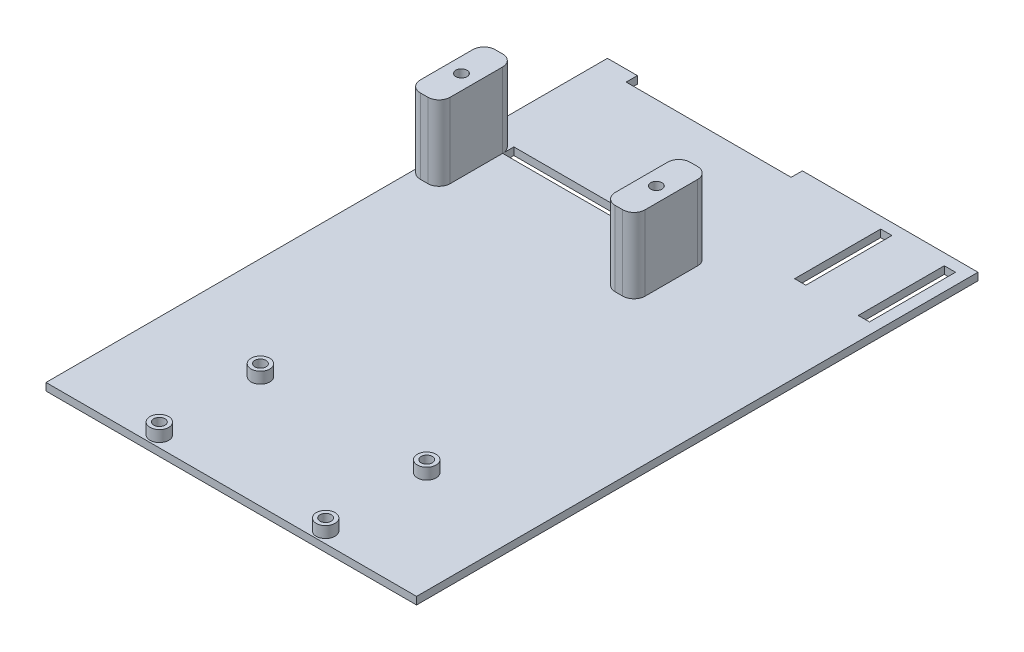
SolidWorks part; units mm, degrees
ref_plane "Front Plane" through (0, 0, 0) normal (0, 0, 1) x (1, 0, 0)
ref_plane "Top Plane" through (0, 0, 0) normal (0, 1, 0) x (1, 0, 0)
ref_plane "Right Plane" through (0, 0, 0) normal (1, 0, 0) x (0, 0, -1)
sketch "Sketch1" plane through (0, 0, 0) normal (0, 1, 0) x (1, 0, 0)
  line L1 (0, 0) -> (99, 0)
  line L2 (0, 0) -> (0, 150)
  line L3 (0, 150) -> (99, 150)
  line L4 (99, 0) -> (99, 150)
  dimension "D1" = 99
  dimension "D2" = 150
extrude "Boss-Extrude1" add sketch "Sketch1" along normal blind 2
sketch "Sketch2" plane through (0, 2, 0) normal (0, 1, 0) x (1, 0, 0)
  line L0 (0, 117) -> (8, 117)
  line L2 (8, 117) -> (8, 97)
  line L3 (8, 97) -> (0, 97)
  line L4 (0, 150) -> (0, 0) construction
  line L5 (0, 97) -> (0, 117)
  line L6 (0, 117) -> (60.075, 117) construction
  line L7 (99, 150) -> (0, 150) construction
  line L8 (60.075, 117) -> (52.075, 117)
  line L9 (60.075, 117) -> (60.075, 97)
  line L10 (60.075, 97) -> (52.075, 97)
  line L11 (52.075, 117) -> (52.075, 97)
  dimension "D1" = 8
  dimension "D2" = 20
  dimension "D3" = 60.075
  dimension "D4" = 8
  dimension "D5" = 20
  dimension "D6" = 33
extrude "Boss-Extrude2" add sketch "Sketch2" along normal blind 20 contours L5 L0 L2 L3 | L9 L8 L11 L10
sketch "Sketch3" plane through (0, 22, 0) normal (0, 1, 0) x (1, 0, 0)
  line L4 (0, 107) -> (8, 107) construction
  line L5 (0, 97) -> (0, 117) construction
  line L6 (8, 117) -> (8, 97) construction
  line L9 (52.075, 107) -> (60.075, 107) construction
  line L10 (52.075, 117) -> (52.075, 97) construction
  line L11 (60.075, 117) -> (60.075, 97) construction
  circle A0 centre (4, 107) radius 1.5
  circle A2 centre (56.075, 107) radius 1.5
  point P2 (4, 109)
  dimension "D1" = 3
  dimension "D2" = 3
  dimension "D3" = 4
  dimension "D4" = 4
  dimension "D5" = 0
extrude "Cut-Extrude2" cut sketch "Sketch3" against normal blind 15 contours A2 | A0 region at (56.075, 22, -107)
sketch "Sketch4" plane through (0, 2, 0) normal (0, 1, 0) x (1, 0, 0)
  line L0 (49.5, 0) -> (49.5, 69.0338) construction
  line L1 (0, 0) -> (99, 0) construction
  line L2 (27.29, 3) -> (71.71, 3) construction
  line L3 (27.29, 3) -> (27.29, 30) construction
  line L4 (27.29, 30) -> (71.71, 30) construction
  line L5 (71.71, 30) -> (71.71, 3) construction
  circle A0 centre (27.29, 30) radius 1.5
  circle A1 centre (71.71, 30) radius 1.5
  circle A2 centre (71.71, 3) radius 1.5
  circle A3 centre (27.29, 3) radius 1.5
  circle A4 centre (27.29, 30) radius 2.5
  circle A5 centre (71.71, 30) radius 2.5
  circle A6 centre (71.71, 3) radius 2.5
  circle A7 centre (27.29, 3) radius 2.5
  dimension "D5" = 3
  dimension "D6" = 3
  dimension "D7" = 3
  dimension "D8" = 3
  dimension "D9" = 5
  dimension "D10" = 5
  dimension "D11" = 5
  dimension "D12" = 5
  dimension "D1" = 3
  dimension "D2" = 44.42
  dimension "D3" = 22.21
  dimension "D4" = 27
extrude "Boss-Extrude4" add sketch "Sketch4" along normal blind 3
sketch "Sketch6" plane through (0, 2, 0) normal (0, 1, 0) x (1, 0, 0)
  line L0 (52.075, 117) -> (52.075, 97) construction
  line L1 (8, 117) -> (52.075, 117)
  line L2 (8, 117) -> (8, 114)
  line L3 (8, 114) -> (52.075, 114)
  line L4 (52.075, 117) -> (52.075, 114)
  line L5 (99, 150) -> (0, 150) construction
  line L6 (8, 150) -> (52.075, 150)
  line L7 (8, 150) -> (8, 147)
  line L8 (8, 147) -> (52.075, 147)
  line L9 (52.075, 150) -> (52.075, 147)
  line L10 (99, 0) -> (99, 150) construction
  line L11 (96, 147) -> (93, 147)
  line L12 (96, 147) -> (96, 124)
  line L13 (96, 124) -> (93, 124)
  line L14 (93, 147) -> (93, 124)
  line L15 (93, 147) -> (79, 147) construction
  line L17 (79, 147) -> (76, 147)
  line L18 (79, 147) -> (79, 124)
  line L19 (79, 124) -> (76, 124)
  line L20 (76, 147) -> (76, 124)
  dimension "D1" = 3
  dimension "D2" = 3
  dimension "D3" = 3
  dimension "D4" = 3
  dimension "D5" = 3
  dimension "D6" = 23
  dimension "D7" = 14
  dimension "D8" = 3
extrude "Cut-Extrude3" cut sketch "Sketch6" against normal blind 4
fillet "Fillet2" radius 3 1 edges at (8, 12, -97) type face fillet first side face at (4, 12, -97) second side face at (8, 7.1429, -110.4286)
fillet "Fillet4" radius 3 1 edges at (0, 12, -97) type face fillet first side face at (2.5, 12, -97) second side face at (0, 6.5, -91)
fillet "Fillet5" radius 3 1 edges at (0, 12, -117) type face fillet first side face at (4, 12, -117) second side face at (0, 6.5, -91.75)
fillet "Fillet6" radius 3 1 edges at (8, 12, -117) type face fillet first side face at (8, 7.1429, -111.2857) second side face at (5.5, 12, -117)
fillet "Fillet7" radius 3 1 edges at (60.075, 12, -97) type face fillet first side face at (60.075, 12, -107) second side face at (56.075, 12, -97)
fillet "Fillet8" radius 3 1 edges at (52.075, 12, -97) type face fillet first side face at (54.575, 12, -97) second side face at (52.075, 7.1429, -110.4286)
fillet "Fillet9" radius 3 1 edges at (60.075, 12, -117) type face fillet first side face at (60.075, 12, -108.5) second side face at (56.075, 12, -117)
fillet "Fillet10" radius 3 1 edges at (52.075, 12, -117) type face fillet first side face at (54.575, 12, -117) second side face at (52.075, 7.1429, -111.2857)
